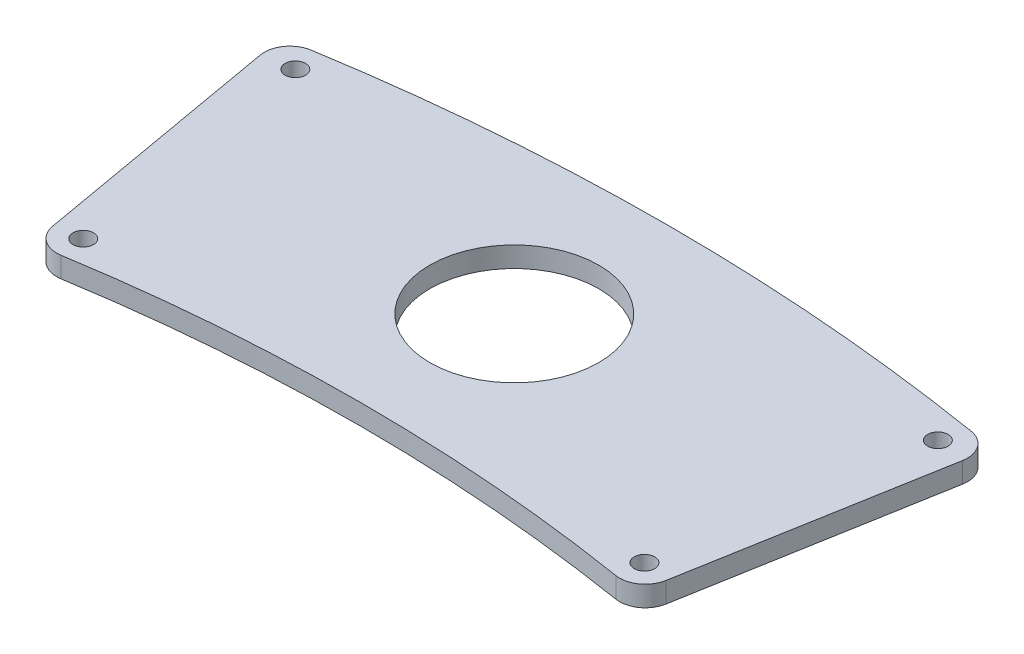
SolidWorks part; units mm, degrees
ref_plane "Спереди" through (0, 0, 0) normal (0, 0, 1) x (1, 0, 0)
ref_plane "Сверху" through (0, 0, 0) normal (0, 1, 0) x (1, 0, 0)
ref_plane "Справа" through (0, 0, 0) normal (1, 0, 0) x (0, 0, -1)
sketch "Эскиз1" plane through (0, 0, 0) normal (0, 1, 0) x (1, 0, 0)
  line L0 (-59.0404, 334.8346) -> (-69.4593, 393.9231) construction
  line L1 (0, 0) -> (0, 340) construction
  line L2 (59.0404, 334.8346) -> (69.4593, 393.9231) construction
  line L3 (-59.0404, 334.8346) -> (-69.4593, 393.9231)
  line L4 (69.4593, 393.9231) -> (59.0404, 334.8346)
  line L10 (0, 400) -> (0, 340) construction
  line L11 (0, 0) -> (-69.4593, 393.9231) construction
  line L12 (0, 0) -> (69.4593, 393.9231) construction
  arc A0 (69.4593, 393.9231) -> (-69.4593, 393.9231) centre (0, 0) ccw construction
  arc A1 (69.4593, 393.9231) -> (-69.4593, 393.9231) centre (0, 0) ccw
  arc A2 (59.0404, 334.8346) -> (-59.0404, 334.8346) centre (0, 0) ccw
  circle A3 centre (0, 370) radius 16.5
  dimension "D1" = 340
  dimension "D2" = 400
  dimension "D3" = 10
  dimension "D4" = 33
  dimension "D5" = 10
sheet metal parameters "Листовой металл1" thickness 4 parameters "D1"=1.2, "Толщина"=4
base flange "Базовая кромка1" sketch "Эскиз1" thickness 4 reverse thickness direction no parameters "D1"=1.2
sketch "Эскиз4" plane through (0, 0, 0) normal (0, 1, 0) x (1, 0, 0)
  line L0 (0, 0) -> (-68.0772, 423.1035) construction
  line L1 (-68.0772, 423.1035) -> (68.0772, 423.1035) construction
  line L2 (68.0772, 423.1035) -> (0, 0) construction
  circle A0 centre (0, 0) radius 345 construction
  circle A1 centre (0, 0) radius 395 construction
  circle A2 centre (62.7483, 389.9842) radius 2
  circle A3 centre (54.8055, 340.6191) radius 2
  circle A4 centre (-54.8055, 340.6191) radius 2
  circle A5 centre (-62.7483, 389.9842) radius 2
  dimension "D1" = 690
  dimension "D2" = 790
  dimension "D5" = 4
  dimension "D6" = 4
  dimension "D7" = 4
  dimension "D8" = 4
  dimension "D3" = 6
  dimension "D4" = 6
extrude "Вырез-Вытянуть1" cut sketch "Эскиз4" against normal blind 10 normal cut yes
fillet "Скругление3" radius 5 4 edges at (-69.4593, -2, -393.9231) (-59.0404, -2, -334.8346) (69.4593, -2, -393.9231) (59.0404, -2, -334.8346)
flat pattern "Развертка1" [suppressed]
sketch "Сгиб-Линии1" plane through (0, 0, 0) normal (0, 1, 0) x (1, 0, 0)
sketch3d "Граничная рамка1" [suppressed]
  line L0 (-105.7369, 160.0484, 0) -> (154.0999, 114.2321, 0) construction
  line L1 (-89.9793, 249.4139, 0) -> (169.8575, 203.5977, 0) construction
  line L2 (-105.7369, 160.0484, 0) -> (-89.9793, 249.4139, 0) construction
  line L3 (154.0999, 114.2321, 0) -> (169.8575, 203.5977, 0) construction
